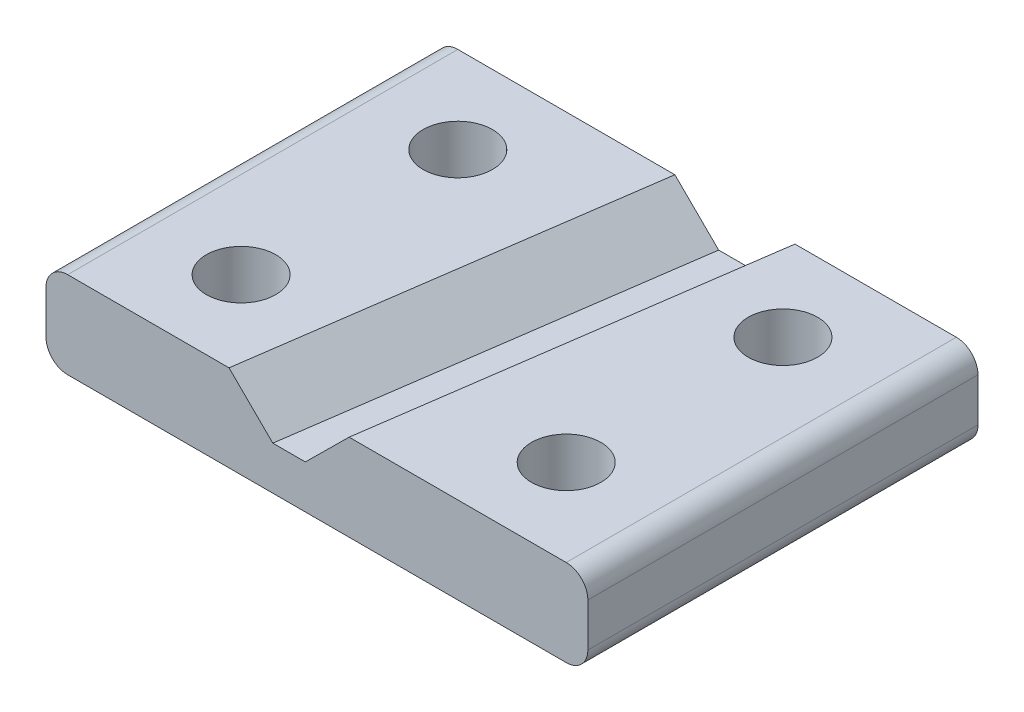
SolidWorks part; units mm, degrees
ref_plane "前视基准面" through (0, 0, 0) normal (0, 0, 1) x (1, 0, 0)
ref_plane "上视基准面" through (0, 0, 0) normal (0, 1, 0) x (1, 0, 0)
ref_plane "右视基准面" through (0, 0, 0) normal (1, 0, 0) x (0, 0, -1)
other "Configuration Table"
sketch "草图1" plane through (0, 0, 0) normal (0, 0, 1) x (1, 0, 0)
  line L0 (-10.5572, 0) -> (15.421, 0) construction
  line L1 (0, 9.9278) -> (0, -8.5545) construction
  line L3 (12.5, -2) -> (-12.5, -2)
  line L4 (12.5, -2) -> (12.5, 2)
  line L5 (12.5, 2) -> (-12.5, 2)
  line L6 (-12.5, -2) -> (-12.5, 2)
  line L7 (12.5, -2) -> (-12.5, 2) construction
  line L8 (12.5, 2) -> (-12.5, -2) construction
  point P4 (0, 0)
  dimension "D1" = 25
  dimension "D2" = 4
extrude "凸台-拉伸1" add sketch "草图1" along normal blind 18
fillet "圆角1" radius 1 4 edges at (12.5, 2, 9) (12.5, -2, 9) (-12.5, 2, 9) (-12.5, -2, 9)
sketch "草图3" plane through (0, -2, 0) normal (0, -1, 0) x (1, 0, 0)
  line L0 (0, -1.7641) -> (0, 20.5985) construction
  line L2 (-19.5454, 9) -> (15.3046, 9) construction
  line L3 (-11.5, 0) -> (11.5, 0) construction
  line L4 (-11.5, 18) -> (11.5, 18) construction
  circle A0 centre (-7.5, 14) radius 1.6
  circle A1 centre (-7.5, 4) radius 1.6
  circle A2 centre (7.5, 4) radius 1.6
  circle A3 centre (7.5, 14) radius 1.6
  dimension "D2" = 3.2
  dimension "D3" = 3.2
  dimension "D1" = 9
  dimension "D4" = 10
  dimension "D5" = 4
  dimension "D6" = 7.5
  dimension "D7" = 7.5
extrude "切除-拉伸2" cut sketch "草图3" against normal through all
sketch "草图4" plane through (0, 2, 0) normal (0, 1, 0) x (1, 0, 0)
  line L1 (11.5, 0) -> (-11.5, 0) construction
  line L2 (11.5, -18) -> (-11.5, -18) construction
  line L3 (5.5709, 0) -> (3, -18)
  line L6 (0, 3.7382) -> (0, -20.1816)
  line L7 (-3, 0) -> (-5.5709, -18)
  line L8 (-3, 0) -> (5.5709, 0)
  line L9 (3, -18) -> (-5.5709, -18)
  dimension "D1" = 3
  dimension "D2" = 3
extrude "切除-拉伸3" cut sketch "草图4" against normal blind 2
chamfer "倒角2" distance 3.5 angle 45 1 edges at (4.2854, 0, 9)
chamfer "倒角3" distance 3.5 angle 45 1 edges at (-4.2854, 0, 9)
